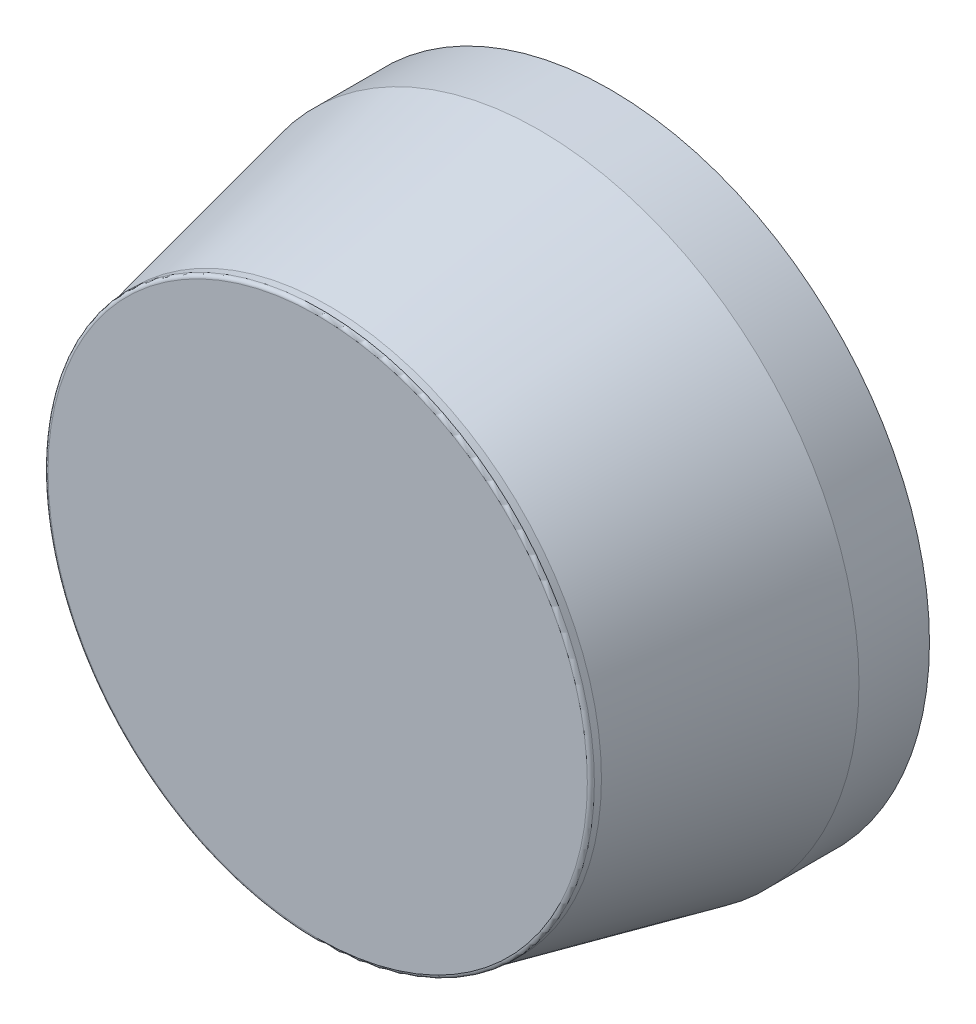
SolidWorks part; units mm, degrees
ref_plane "Front Plane" through (0, 0, 0) normal (0, 0, 1) x (1, 0, 0)
ref_plane "Top Plane" through (0, 0, 0) normal (0, 1, 0) x (1, 0, 0)
ref_plane "Right Plane" through (0, 0, 0) normal (1, 0, 0) x (0, 0, -1)
sketch "Sketch1" plane through (0, 0, 0) normal (0, 0, 1) x (1, 0, 0)
  circle A0 centre (0, 0) radius 90.55
  circle A1 centre (0, 0) radius 87.55
  dimension "D1" = 181.1
  dimension "D2" = 3
ref_plane "Plane1" through (0, 0, 60) normal (0, 0, 1) x (1, 0, 0)
sketch "Sketch2" plane through (0, 0, 60) normal (0, 0, 1) x (1, 0, 0)
  circle A0 centre (0, 0) radius 77.5
  circle A1 centre (0, 0) radius 74.5
  dimension "D1" = 155
  dimension "D2" = 3
loft "Loft2" add section "Sketch2" section "Sketch1" connector at (73.2583, 25.2878, 60) connector at (88.9032, 17.1909, 0)
sketch "Sketch3" plane through (0, 0, 0) normal (0, 0, -1) x (-1, 0, 0)
  circle A0 centre (0, 0) radius 87.05
sketch "Sketch4" plane through (0, 0, 60) normal (0, 0, 1) x (1, 0, 0)
  circle A0 centre (0, 0) radius 74.5
loft "Cut-Loft1" cut profiles "Sketch4", "Sketch3" connector at (-2.2577, 74.4658, 60) connector at (2.664, 87.0092, 0)
sketch "Sketch5" plane through (0, 0, 60) normal (0, 0, 1) x (1, 0, 0)
  circle A0 centre (0, 0) radius 77.5
extrude "Boss-Extrude1" add sketch "Sketch5" along normal blind 3
sketch "Sketch6" plane through (0, 0, 0) normal (0, 0, -1) x (-1, 0, 0)
  circle A0 centre (0, 0) radius 90.55
  circle A1 centre (0, 0) radius 87.05
sketch "Sketch7" plane through (0, 0, 0) normal (0, 1, 0) x (1, 0, 0)
  circle A0 centre (0, -36.3969) radius 20
extrude "Cut-Extrude1" cut sketch "Sketch7" against normal blind 159
sketch "Sketch9" plane through (0, 0, 0) normal (1, 0, 0) x (0, 0, -1)
  line L1 (-50.6037, 3.6296) -> (-19.7524, 3.6296)
  line L2 (-50.6037, 3.6296) -> (-50.6037, -3.6296)
  line L3 (-50.6037, -3.6296) -> (-19.7524, -3.6296)
  line L4 (-19.7524, 3.6296) -> (-19.7524, -3.6296)
  line L5 (-50.6037, 3.6296) -> (-19.7524, -3.6296) construction
  line L6 (-50.6037, -3.6296) -> (-19.7524, 3.6296) construction
  point P0 (-35.1781, 0)
extrude "Boss-Extrude4" add sketch "Sketch9" along normal up to surface and the other way up to surface up to face at (11.5974, -75.139, 52.6911) other way up to face at (11.5974, -75.139, 52.6911)
fillet "Fillet2" radius 1 1 edges at (77.5, 0, 63)
extrude "Boss-Extrude6" add sketch "Sketch1<7>" against normal blind 20
sketch "Sketch1<7>" plane through (0, 0, 0) normal (0, 0, 1) x (1, 0, 0) same geometry as "Sketch1"
